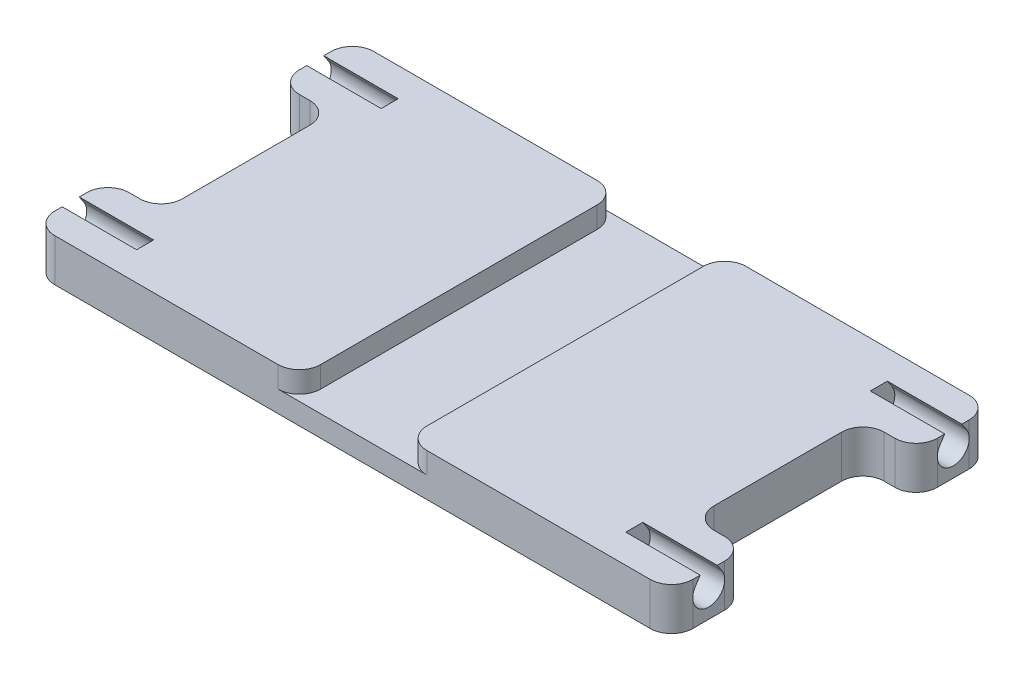
SolidWorks part; units mm, degrees
material "99.5% Aluminum Oxide"
ref_plane "Front Plane" through (0, 0, 0) normal (0, 0, 1) x (1, 0, 0)
ref_plane "Top Plane" through (0, 0, 0) normal (0, 1, 0) x (1, 0, 0)
ref_plane "Right Plane" through (0, 0, 0) normal (1, 0, 0) x (0, 0, -1)
sketch "Sketch2" plane through (0, 0, 0) normal (0, 1, 0) x (1, 0, 0)
  line L0 (-25, -8) -> (-30, -8)
  line L1 (-25, -15) -> (25, -15) construction
  line L2 (-25, -15) -> (-25, 15) construction
  line L3 (-25, 15) -> (25, 15) construction
  line L4 (25, -15) -> (25, 15) construction
  line L5 (-25, -15) -> (25, 15) construction
  line L6 (-25, 15) -> (25, -15) construction
  line L7 (-30, -8) -> (-30, -15)
  line L8 (-30, -15) -> (30, -15)
  line L9 (30, -15) -> (30, -8)
  line L10 (30, -8) -> (25, -8)
  line L11 (25, -8) -> (25, 8)
  line L12 (25, 8) -> (30, 8)
  line L13 (30, 8) -> (30, 15)
  line L14 (30, 15) -> (-30, 15)
  line L15 (-30, 15) -> (-30, 8)
  line L16 (-30, 8) -> (-25, 8)
  line L17 (-25, 8) -> (-25, -8)
  point P0 (0, 0)
  point P18 (-25, -6.6746)
  dimension "D1" = 30
  dimension "D2" = 50
  dimension "D3" = 5
  dimension "D4" = 7
extrude "Boss-Extrude1" add sketch "Sketch2" along normal mid plane 4
sketch "Sketch3" plane through (30, 0, 0) normal (1, 0, 0) x (0, 0, -1)
  line L0 (-11.5, -2) -> (-11.5, 0.5) construction
  line L1 (-12.3, 2) -> (-12.7457, 1.3356)
  line L2 (-15, -2) -> (-8, -2) construction
  line L3 (-10.7, 2) -> (-10.2543, 1.3356)
  line L4 (-15, 2) -> (-8, 2) construction
  line L5 (-12.3, 2) -> (-10.7, 2)
  arc A1 (-12.7457, 1.3356) -> (-10.2543, 1.3356) centre (-11.5, 0.5) ccw
  arc A4 (-10.2543, 1.3356) -> (-12.7457, 1.3356) centre (-11.5, 0.5) ccw construction
  dimension "D2" = 1.5
  dimension "D1" = 2.5
  dimension "D3" = 1.6
extrude "Cut-Extrude1" cut sketch "Sketch3" against normal blind 7
mirror "Mirror1" about plane through (0, 0, 0) normal (1, 0, 0) of "Cut-Extrude1"
mirror "Mirror2" about plane through (0, 0, 0) normal (0, 0, 1) of "Mirror1", "Cut-Extrude1"
sketch "Sketch4" plane through (0, 2, 0) normal (0, 1, 0) x (1, 0, 0)
  line L0 (30, 15) -> (-30, 15) construction
  line L1 (-5, -15) -> (5, -15)
  line L2 (-5, -15) -> (-5, 15)
  line L3 (-5, 15) -> (5, 15)
  line L4 (5, -15) -> (5, 15)
  line L5 (-5, -15) -> (5, 15) construction
  line L6 (-5, 15) -> (5, -15) construction
  point P0 (0, 0)
  dimension "D1" = 10
  dimension "D2" = 30
  dimension "D3" = 10
extrude "Cut-Extrude2" cut sketch "Sketch4" against normal blind 2
fillet "Fillet1" radius 2 16 edges at (5, 1, -15) (5, 1, 15) (-5, 1, 15) (-5, 1, -15) (-25, 0, 8) (-30, 0, 8) (-30, 0, 15) (30, 0, 15) (25, 0, 8) (25, 0, -8) (30, 0, -8) (30, 0, -15) (-30, 0, -15) (-30, 0, -8) (-25, 0, -8) (30, 0, 8)
